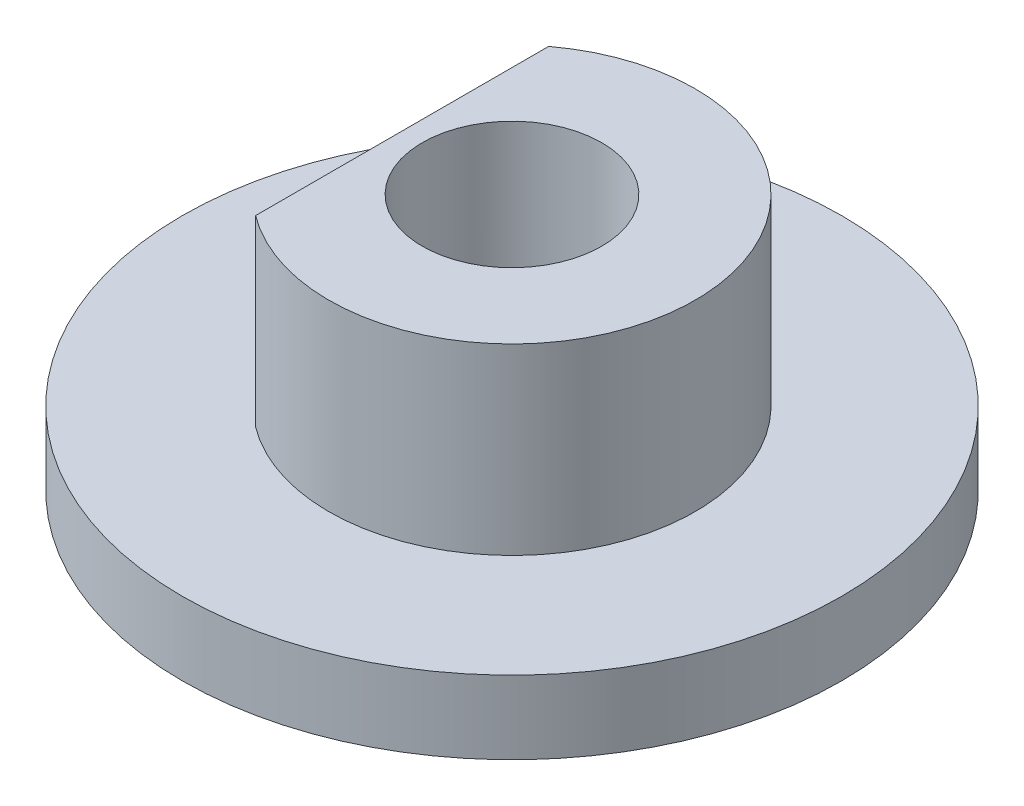
SolidWorks part; units mm, degrees
ref_plane "Front Plane" through (0, 0, 0) normal (0, 0, 1) x (1, 0, 0)
ref_plane "Top Plane" through (0, 0, 0) normal (0, 1, 0) x (1, 0, 0)
ref_plane "Right Plane" through (0, 0, 0) normal (1, 0, 0) x (0, 0, -1)
sketch "Sketch1" plane through (0, 0, 0) normal (0, 1, 0) x (1, 0, 0)
  line L0 (-3, 4) -> (-3, -4)
  circle A0 centre (0, 0) radius 9
  circle A1 centre (0, 0) radius 5
  point P7 (0, 0)
  dimension "D1" = 18
  dimension "D2" = 10
  dimension "D3" = 3
extrude "key-Extrude" add sketch "Sketch1" along normal blind 7 contours L0 A1 region at (0.6334, 0, 0)
extrude "base-Extrude" add sketch "Sketch1<6>" along normal blind 2 separate body contours A0 A1 | A1 region at (-8.7454, 0, 0)
sketch "Sketch1<6>" plane through (0, 0, 0) normal (0, 1, 0) x (1, 0, 0) same geometry as "Sketch1"
sketch "Sketch2" plane through (0, 0, 0) normal (0, -1, 0) x (1, 0, 0)
  circle A0 centre (0, 0) radius 2.45
  dimension "D1" = 4.9
extrude "motorshaft-Cut" cut sketch "Sketch2" against normal through all both and the other way through all
